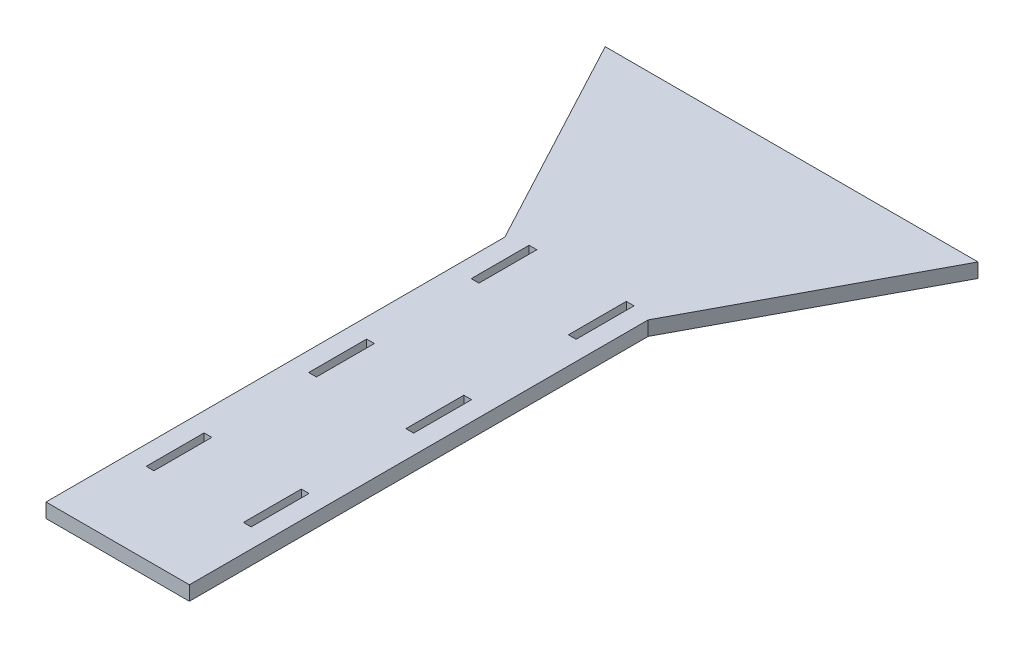
SolidWorks part; units mm, degrees
material "PC High Viscosity"
ref_plane "Front" through (0, 0, 0) normal (0, 0, 1) x (1, 0, 0)
ref_plane "Top" through (0, 0, 0) normal (0, 1, 0) x (1, 0, 0)
ref_plane "Right" through (0, 0, 0) normal (1, 0, 0) x (0, 0, -1)
sketch "Sketch1" plane through (0, 0, 0) normal (0, 1, 0) x (1, 0, 0)
  line L0 (-31.75, 0) -> (31.75, 0)
  line L1 (31.75, 0) -> (31.75, 203.2)
  line L2 (31.75, 203.2) -> (82.55, 298.45)
  line L3 (82.55, 298.45) -> (-82.55, 298.45)
  line L4 (-82.55, 298.45) -> (-31.75, 203.2)
  line L5 (-31.75, 203.2) -> (-31.75, 0)
  point P4 (0, 0)
  dimension "D1" = 63.5
  dimension "D2" = 203.2
  dimension "D3" = 95.25
  dimension "D4" = 165.1
extrude "Boss-Extrude1" add sketch "Sketch1" along normal blind 6.35
sketch "Sketch2" plane through (0, 6.35, 0) normal (0, 1, 0) x (1, 0, 0)
  line L4 (-23.241, 61.5103) -> (-23.241, 35.8563)
  line L5 (-23.241, 35.8563) -> (-19.812, 35.8563)
  line L6 (-19.812, 35.8563) -> (-19.812, 61.5103)
  line L7 (-19.812, 61.5103) -> (-23.241, 61.5103)
  line L8 (-23.241, 61.5103) -> (-23.241, 35.8563)
  line L9 (-23.241, 35.8563) -> (-19.812, 35.8563)
  line L10 (-19.812, 35.8563) -> (-19.812, 61.5103)
  line L11 (-19.812, 61.5103) -> (-23.241, 61.5103)
  line L12 (-23.241, 133.477) -> (-23.241, 107.823)
  line L13 (-23.241, 107.823) -> (-19.812, 107.823)
  line L14 (-19.812, 107.823) -> (-19.812, 133.477)
  line L15 (-19.812, 133.477) -> (-23.241, 133.477)
  line L16 (-23.241, 133.477) -> (-23.241, 107.823)
  line L17 (-23.241, 107.823) -> (-19.812, 107.823)
  line L18 (-19.812, 107.823) -> (-19.812, 133.477)
  line L19 (-19.812, 133.477) -> (-23.241, 133.477)
  line L24 (-23.241, 205.4437) -> (-23.241, 179.7897)
  line L25 (-23.241, 179.7897) -> (-19.812, 179.7897)
  line L26 (-19.812, 179.7897) -> (-19.812, 205.4437)
  line L27 (-19.812, 205.4437) -> (-23.241, 205.4437)
  line L28 (-23.241, 205.4437) -> (-23.241, 179.7897)
  line L29 (-23.241, 179.7897) -> (-19.812, 179.7897)
  line L30 (-19.812, 179.7897) -> (-19.812, 205.4437)
  line L31 (-19.812, 205.4437) -> (-23.241, 205.4437)
  line L36 (19.812, 205.4437) -> (19.812, 179.7897)
  line L37 (19.812, 179.7897) -> (23.241, 179.7897)
  line L38 (23.241, 179.7897) -> (23.241, 205.4437)
  line L39 (23.241, 205.4437) -> (19.812, 205.4437)
  line L40 (19.812, 205.4437) -> (19.812, 179.7897)
  line L41 (19.812, 179.7897) -> (23.241, 179.7897)
  line L42 (23.241, 179.7897) -> (23.241, 205.4437)
  line L43 (23.241, 205.4437) -> (19.812, 205.4437)
  line L48 (19.812, 133.477) -> (19.812, 107.823)
  line L49 (19.812, 107.823) -> (23.241, 107.823)
  line L50 (23.241, 107.823) -> (23.241, 133.477)
  line L51 (23.241, 133.477) -> (19.812, 133.477)
  line L52 (19.812, 133.477) -> (19.812, 107.823)
  line L53 (19.812, 107.823) -> (23.241, 107.823)
  line L54 (23.241, 107.823) -> (23.241, 133.477)
  line L55 (23.241, 133.477) -> (19.812, 133.477)
  line L60 (19.812, 61.5103) -> (19.812, 35.8563)
  line L61 (19.812, 35.8563) -> (23.241, 35.8563)
  line L62 (23.241, 35.8563) -> (23.241, 61.5103)
  line L63 (23.241, 61.5103) -> (19.812, 61.5103)
  line L64 (19.812, 61.5103) -> (19.812, 35.8563)
  line L65 (19.812, 35.8563) -> (23.241, 35.8563)
  line L66 (23.241, 35.8563) -> (23.241, 61.5103)
  line L67 (23.241, 61.5103) -> (19.812, 61.5103)
  dimension "D1" = 0.127
  dimension "D2" = 0.127
  dimension "D3" = 0.127
  dimension "D4" = 0.127
  dimension "D5" = 0.127
  dimension "D6" = 0.127
extrude "Cut-Extrude1" cut sketch "Sketch2" against normal through all
